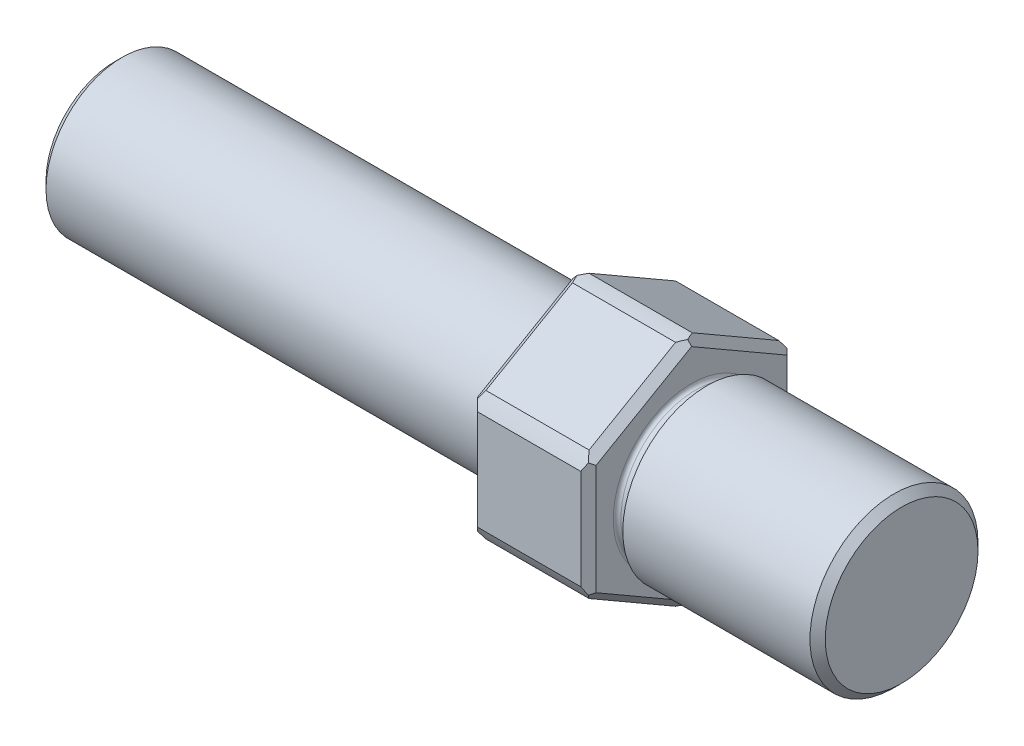
SolidWorks part; units mm, degrees
material "AISI 1010 Barra de acero laminada en caliente"
ref_plane "Alzado" through (0, 0, 0) normal (0, 0, 1) x (1, 0, 0)
ref_plane "Planta" through (0, 0, 0) normal (0, 1, 0) x (1, 0, 0)
ref_plane "Vista lateral" through (0, 0, 0) normal (1, 0, 0) x (0, 0, -1)
sketch "Croquis1" plane through (0, 0, 0) normal (0, 1, 0) x (1, 0, 0)
  line L0 (0, 0) -> (-104, 0) construction
  line L1 (0, 0) -> (0, 11)
  line L2 (0, 11) -> (-50, 11)
  line L5 (-54, 11) -> (-54, 10)
  line L6 (-54, 10) -> (-104, 10)
  line L7 (-104, 10) -> (-104, 0)
  line L8 (0, 0) -> (-104, 0)
  line L10 (-54, 11) -> (-50, 11)
  dimension "D1" = 22
  dimension "D3" = 20
  dimension "D4" = 50
  dimension "D6" = 50
revolve "Revolución1" add sketch "Croquis1" angle 360 about L0
chamfer "Chaflán1" distance 1 angle 45 1 edges at (0, 0, -11)
fillet "Redondeo1" radius 1 1 edges at (-54, 0, -10)
sketch "Croquis2" plane through (0, 0, 0) normal (1, 0, 0) x (0, 0, -1)
  circle A0 centre (0, 0) radius 21.7769
extrude "Cortar-Extruir1" cut sketch "Croquis2" against normal blind 11
chamfer "Chaflán2" distance 1 angle 45 1 edges at (-11, 0, -11)
ref_plane "Plano1" through (-54, 0, 0) normal (1, 0, 0) x (0, 0, -1)
sketch "Croquis10" plane through (-54, 0, 0) normal (1, 0, 0) x (0, 0, -1)
  line L1 (-13.5, 7.7942) -> (-13.5, -7.7942)
  line L2 (-13.5, -7.7942) -> (0, -15.5885)
  line L3 (0, -15.5885) -> (13.5, -7.7942)
  line L4 (13.5, -7.7942) -> (13.5, 7.7942)
  line L5 (13.5, 7.7942) -> (0, 15.5885)
  line L6 (0, 15.5885) -> (-13.5, 7.7942)
  circle A0 centre (0, 0) radius 13.5 construction
  dimension "D1" = 27
extrude "Saliente-Extruir1" add sketch "Croquis10" along normal blind 15.5
sketch "Croquis3" plane through (-11, 0, 0) normal (1, 0, 0) x (0, 0, -1)
  circle A0 centre (0, 0) radius 34.6949
sketch "Croquis12" plane through (0, 0, 0) normal (0, 1, 0) x (1, 0, 0)
  line L1 (-38.5, -11.75) -> (-36.5, -11.75)
  line L2 (-38.5, -11.75) -> (-38.5, -9.75)
  line L3 (-38.5, -9.75) -> (-36.5, -9.75)
  line L4 (-36.5, -11.75) -> (-36.5, -9.75)
  line L5 (-38.5, -11.75) -> (-36.5, -9.75) construction
  line L6 (-38.5, -9.75) -> (-36.5, -11.75) construction
  line L7 (-11, -34.6949) -> (-11, 34.6949) construction
  line L8 (0, 0) -> (-120.3997, 0) construction
  point P0 (-37.5, -10.75)
  dimension "D1" = 2
  dimension "D2" = 2
  dimension "D3" = 19.5
  dimension "D4" = 27.5
revolve "Cortar-Revolución1" cut sketch "Croquis12" angle 360 about L8
fillet "Redondeo3" radius 0.5 1 edges at (-38.5, 0, -9.75)
sketch "Croquis15" plane through (-104, 0, 0) normal (-1, 0, 0) x (0, 0, 1)
  circle A1 centre (0, 0) radius 10
  circle A2 centre (0, 0) radius 10
  dimension "D1" = 0
extrude "Saliente-Extruir3" add sketch "Croquis15" along normal blind 10
chamfer "Chaflán6" distance 1 angle 45 1 edges at (-114, 0, 10)
sketch "Croquis16" plane through (-54, 0, 0) normal (-1, 0, 0) x (0, 0, 1)
  circle A0 centre (0, 0) radius 15
  circle A1 centre (0, 0) radius 17.5
  dimension "D1" = 30
  dimension "D2" = 35
chamfer "Chaflán8" distance 1 angle 45 12 edges at (-38.5, 0, 13.5) (-38.5, -11.6913, 6.75) (-38.5, -11.6913, -6.75) (-38.5, 11.6913, 6.75) (-38.5, 11.6913, -6.75) (-38.5, 0, -13.5) (-54, 11.6913, 6.75) (-54, 11.6913, -6.75) (-54, 0, 13.5) (-54, -11.6913, 6.75) (-54, 0, -13.5) (-54, -11.6913, -6.75)
sketch "Croquis17" plane through (-54, 0, 0) normal (-1, 0, 0) x (0, 0, 1)
  circle A0 centre (0, 0) radius 15
  circle A1 centre (0, 0) radius 19.7009
  dimension "D1" = 30
extrude "Cortar-Extruir3" cut sketch "Croquis17" against normal up to surface (15.5 mm away) up to face at (-38.5, 0, 0)
